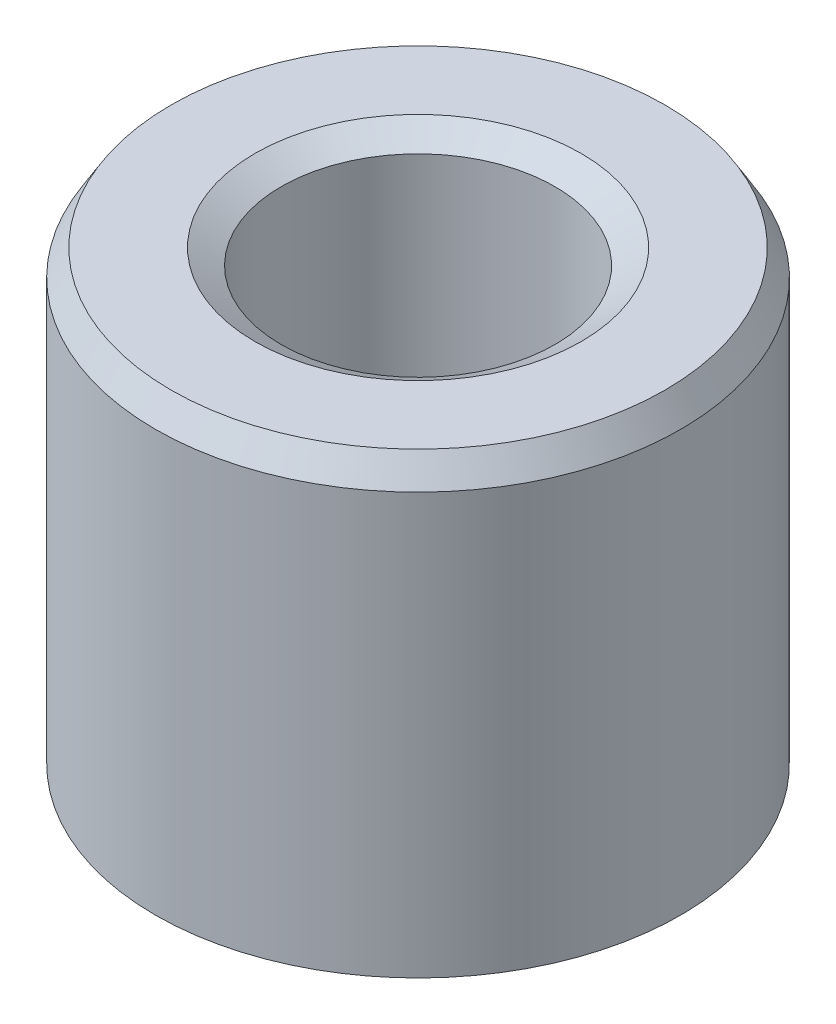
SolidWorks part; units mm, degrees
ref_plane "Front Plane" through (0, 0, 0) normal (0, 0, 1) x (1, 0, 0)
ref_plane "Top Plane" through (0, 0, 0) normal (0, 1, 0) x (1, 0, 0)
ref_plane "Right Plane" through (0, 0, 0) normal (1, 0, 0) x (0, 0, -1)
sketch "Sketch1" plane through (0, 0, 0) normal (0, 1, 0) x (1, 0, 0)
  circle A0 centre (0, 0) radius 10
  dimension "SLEEVE_OD" = 20
extrude "Boss-Extrude1" add sketch "Sketch1" along normal blind 17.6137
sketch "Sketch2" plane through (0, 0, 0) normal (0, 1, 0) x (1, 0, 0)
  circle A0 centre (0, 0) radius 5.2115
  dimension "BORE_D" = 10.4231
extrude "Cut-Extrude1" cut sketch "Sketch2" along normal through all
chamfer "Chamfer1" distance 0.9972 angle 30.863 4 edges at (0, 17.6137, 5.2115) (0, 0, 5.2115) (0, 0, 10) (0, 17.6137, 10) first distance on face at (0, 17.6137, 5.2115) first distance on face at (0, 0, 5.2115) first distance on face at (0, 17.6137, 10)
